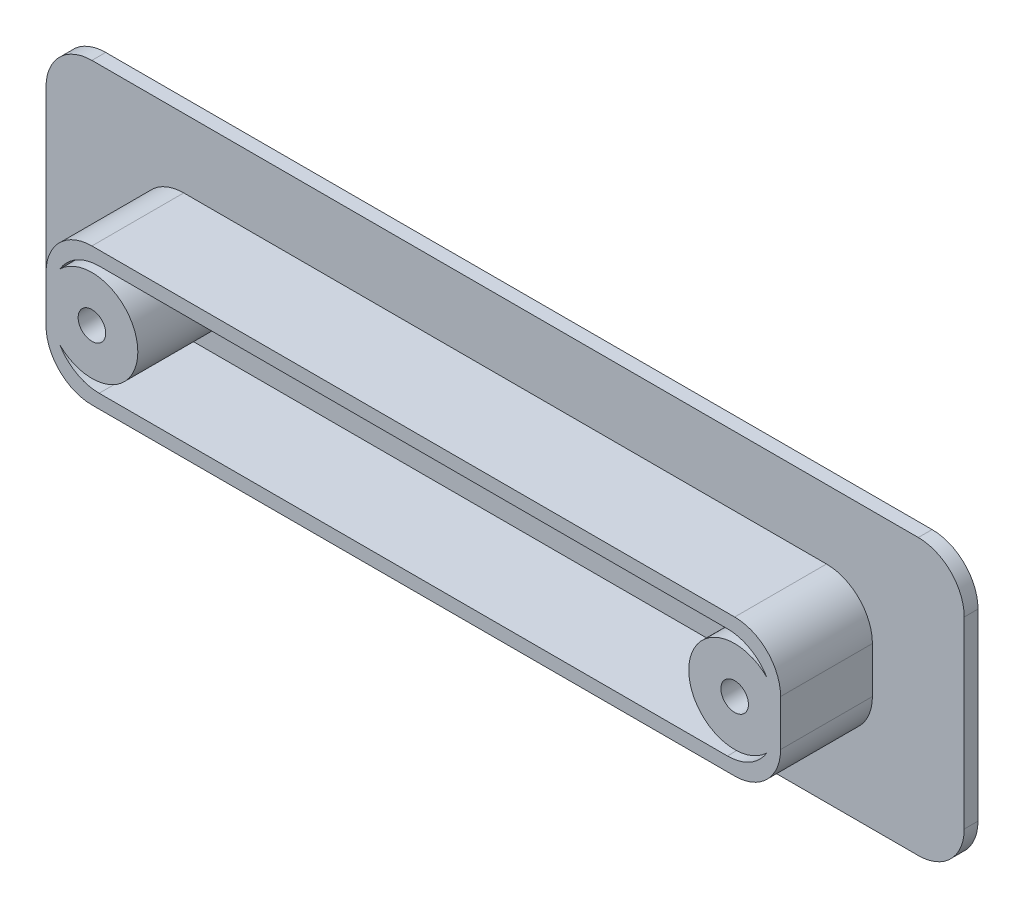
SolidWorks part; units mm, degrees
ref_plane "Front Plane" through (0, 0, 0) normal (0, 0, 1) x (1, 0, 0)
ref_plane "Top Plane" through (0, 0, 0) normal (0, 1, 0) x (1, 0, 0)
ref_plane "Right Plane" through (0, 0, 0) normal (1, 0, 0) x (0, 0, -1)
sketch "Sketch1" plane through (0, 0, 0) normal (0, 0, 1) x (1, 0, 0)
  line L1 (-50, 15) -> (50, 15)
  line L2 (-50, 15) -> (-50, -15)
  line L3 (-50, -15) -> (50, -15)
  line L4 (50, 15) -> (50, -15)
  line L5 (-50, 15) -> (50, -15) construction
  line L6 (-50, -15) -> (50, 15) construction
  point P0 (0, 0)
  dimension "D1" = 100
  dimension "D2" = 30
extrude "Boss-Extrude1" add sketch "Sketch1" along normal blind 1.5
sketch "Sketch2" plane through (0, 0, 1.5) normal (0, 0, 1) x (1, 0, 0)
  line L1 (-40, 7.5) -> (40, 7.5)
  line L2 (-40, 7.5) -> (-40, -7.5)
  line L3 (-40, -7.5) -> (40, -7.5)
  line L4 (40, 7.5) -> (40, -7.5)
  line L5 (-40, 7.5) -> (40, -7.5) construction
  line L6 (-40, -7.5) -> (40, 7.5) construction
  point P0 (0, 0)
  dimension "D1" = 80
  dimension "D2" = 15
extrude "Extrude-Thin1" add sketch "Sketch2" along normal blind 10 thin thin type one direction reverse wall 1.5
sketch "Sketch3" plane through (0, 0, 1.5) normal (0, 0, 1) x (1, 0, 0)
  line L0 (0, 12.3228) -> (0, -10.7897) construction
  circle A0 centre (-35, 0) radius 5
  circle A1 centre (35, 0) radius 5
  dimension "D1" = 10
  dimension "D2" = 35
extrude "Boss-Extrude2" add sketch "Sketch3" along normal up to surface (10 mm away) up to face at (0, 0, 11.5)
sketch "Sketch4" plane through (0, 0, 11.5) normal (0, 0, 1) x (1, 0, 0)
  line L0 (0, 11.031) -> (0, -19.5989) construction
  circle A0 centre (-35, 0) radius 1.5
  circle A1 centre (35, 0) radius 1.5
  dimension "D1" = 3
extrude "Cut-Extrude1" cut sketch "Sketch4" against normal blind 10
fillet "Fillet1" radius 5 12 edges at (40, 7.5, 6.5) (40, -7.5, 6.5) (-40, 7.5, 6.5) (-40, -7.5, 6.5) (-50, 15, 0.75) (-50, -15, 0.75) (50, -15, 0.75) (50, 15, 0.75) (38.5, -6, 6.5) (38.5, 6, 6.5) (-38.5, -6, 6.5) (-38.5, 6, 6.5)
